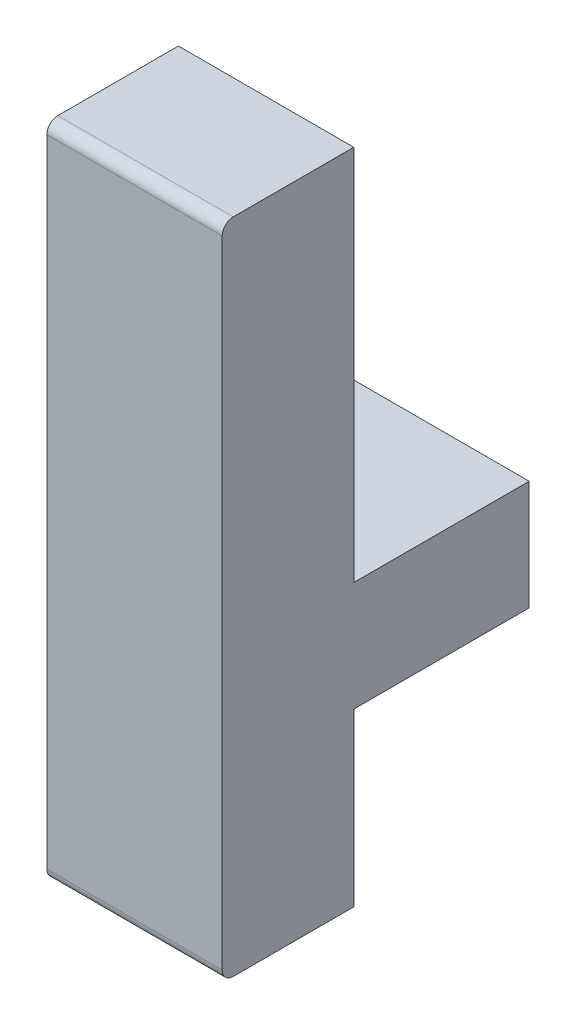
SolidWorks part; units mm, degrees
ref_plane "前视基准面" through (0, 0, 0) normal (0, 0, 1) x (1, 0, 0)
ref_plane "上视基准面" through (0, 0, 0) normal (0, 1, 0) x (1, 0, 0)
ref_plane "右视基准面" through (0, 0, 0) normal (1, 0, 0) x (0, 0, -1)
sketch "草图1" plane through (0, 0, 0) normal (1, 0, 0) x (0, 0, -1)
  line L0 (-2.6373, 0) -> (8.8739, 0) construction
  line L1 (0, -15) -> (6, -15)
  line L2 (0, -15) -> (0, 15)
  line L3 (0, 15) -> (6, 15)
  line L4 (6, -15) -> (6, 15)
  dimension "D1" = 6
  dimension "D2" = 30
extrude "凸台-拉伸1" add sketch "草图1" along normal blind 8
sketch "草图2" plane through (8, 0, 0) normal (1, 0, 0) x (0, 0, -1)
  line L1 (6, -7.19) -> (14, -7.19)
  line L2 (6, -7.19) -> (6, -2.19)
  line L3 (6, -2.19) -> (14, -2.19)
  line L4 (14, -7.19) -> (14, -2.19)
  line L5 (6, -15) -> (6, 15) construction
  dimension "D1" = 5
  dimension "D2" = 8
  dimension "D3" = 7.81
extrude "凸台-拉伸2" add sketch "草图2" against normal up to surface (8 mm away) up to face at (0, 0, -3)
fillet "圆角1" radius 0.5 2 edges at (4, -15, 0) (4, 15, 0)
